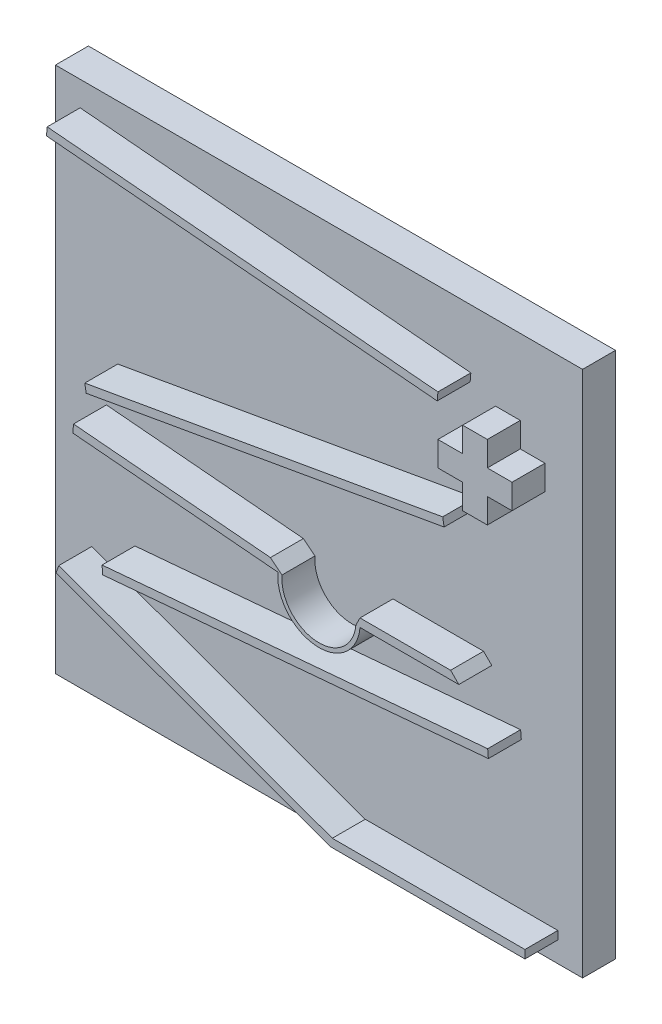
SolidWorks part; units mm, degrees
ref_plane "Front Plane" through (0, 0, 0) normal (0, 0, 1) x (1, 0, 0)
ref_plane "Top Plane" through (0, 0, 0) normal (0, 1, 0) x (1, 0, 0)
ref_plane "Right Plane" through (0, 0, 0) normal (1, 0, 0) x (0, 0, -1)
sketch "Sketch1" plane through (0, 0, 0) normal (0, 0, 1) x (1, 0, 0)
  line L0 (-348.7355, 289.6567) -> (-349.607, 279.6948)
  line L1 (-358.7355, 299.6567) -> (241.2645, 299.6567)
  line L2 (-358.7355, 299.6567) -> (-358.7355, -300.3433)
  line L3 (-358.7355, -300.3433) -> (241.2645, -300.3433)
  line L4 (241.2645, 299.6567) -> (241.2645, -300.3433)
  line L5 (-378.7355, 319.6567) -> (261.2645, 319.6567)
  line L6 (-378.7355, 319.6567) -> (-378.7355, -320.3433)
  line L7 (-378.7355, -320.3433) -> (261.2645, -320.3433)
  line L8 (261.2645, 319.6567) -> (261.2645, -320.3433)
  line L9 (-348.7355, 289.6567) -> (125.6342, 248.1548)
  line L10 (-349.607, 279.6948) -> (124.7627, 238.1928)
  line L11 (124.7627, 238.1928) -> (125.6342, 248.1548)
  line L12 (125.6342, 198.1548) -> (125.6342, 168.1548)
  line L13 (125.6342, 198.1548) -> (155.6342, 198.1548)
  line L14 (125.6342, 168.1548) -> (155.6342, 168.1548)
  line L15 (155.6342, 168.1548) -> (155.6342, 138.1548)
  line L16 (155.6342, 138.1548) -> (185.6342, 138.1548)
  line L17 (185.6342, 138.1548) -> (185.6342, 168.1548)
  line L18 (185.6342, 168.1548) -> (215.6342, 168.1548)
  line L19 (215.6342, 168.1548) -> (215.6342, 198.1548)
  line L20 (215.6342, 198.1548) -> (185.6342, 198.1548)
  line L21 (185.6342, 198.1548) -> (185.6342, 228.1548)
  line L22 (185.6342, 228.1548) -> (155.6342, 228.1548)
  line L23 (155.6342, 228.1548) -> (155.6342, 198.1548)
  line L24 (131.444, 119.6567) -> (-303.1276, 43.03)
  line L25 (-303.1276, 43.03) -> (-301.3911, 33.1819)
  line L26 (-301.3911, 33.1819) -> (133.1805, 109.8086)
  line L27 (131.444, 119.6567) -> (133.1805, 109.8086)
  line L28 (-316.7965, -6.8181) -> (-77.7098, -27.7354)
  line L29 (-316.7965, -6.8181) -> (-317.6681, -16.78)
  line L30 (-317.6681, -16.78) -> (-68.6194, -38.5689)
  line L31 (-77.7098, -27.7354) -> (-63.6384, -39.0047)
  line L32 (-316.7965, -6.8181) -> (-264.7629, -6.8181) construction
  line L33 (31.0363, -46.8487) -> (151.0363, -46.8487)
  line L34 (31.0363, -36.8487) -> (141.0363, -36.8487)
  line L35 (141.0363, -36.8487) -> (151.0363, -46.8487)
  line L36 (186.0363, -96.8487) -> (-282.1752, -137.8119)
  line L37 (26.0191, -46.8487) -> (31.0363, -36.8487)
  line L38 (-282.1752, -137.8119) -> (-281.3037, -147.7739)
  line L39 (-281.3037, -147.7739) -> (186.9078, -106.8107)
  line L40 (186.0363, -96.8487) -> (186.9078, -106.8107)
  line L41 (186.0363, -96.8487) -> (134.5722, -96.8487) construction
  line L42 (-334.5739, -164.5144) -> (-2.5993, -285.3433)
  line L43 (231.2645, -285.3433) -> (231.2645, -295.3433)
  line L44 (-4.3626, -295.3433) -> (-337.9941, -173.9113)
  line L45 (-337.9941, -173.9113) -> (-334.5739, -164.5144)
  line L46 (-334.5739, -164.5144) -> (-283.0811, -164.5144) construction
  line L47 (-2.5993, -285.3433) -> (231.2645, -285.3433)
  line L48 (-4.3626, -295.3433) -> (231.2645, -295.3433)
  arc A0 (-68.6194, -38.5689) -> (31.0363, -46.8487) centre (-18.8097, -42.9267) ccw
  arc A1 (-63.6384, -39.0047) -> (26.0191, -46.8487) centre (-18.8097, -42.9267) ccw
  point P0 (0, 0)
  point P6 (0, 0)
  point P50 (0, 0)
  point P57 (0, 0)
  point P58 (0, 0)
  point P59 (230.0478, -295.3433)
  dimension "D15" = 40
  dimension "D18" = 100
  dimension "D19" = 90
  dimension "D1" = 600
  dimension "D2" = 600
  dimension "D3" = 20
  dimension "D4" = 640
  dimension "D5" = 20
  dimension "D6" = 640
  dimension "D7" = 5
  dimension "D8" = 10
  dimension "D9" = 10
  dimension "D10" = 10
  dimension "D11" = 30
  dimension "D12" = 20
  dimension "D13" = 30
  dimension "D14" = 10
  dimension "D16" = 180
  dimension "D17" = 250
  dimension "D20" = 240
  dimension "D21" = 5
  dimension "D22" = 10
  dimension "D23" = 120
  dimension "D24" = 110
  dimension "D25" = 50
  dimension "D26" = 35
  dimension "D27" = 470
  dimension "D28" = 5
  dimension "D29" = 20
  dimension "D30" = 5
  dimension "D31" = 10
  dimension "D32" = 10
extrude "Boss-Extrude2" add sketch "Sketch1" along normal blind 40 separate body contours L22 L23 L13 L12 L14 L15 L16 L17 L18 L19 L20 L21 | L10 L11 L9 L0 | L26 L27 L24 L25 | L28 L31 A1 L37 L34 L35 L33 A0 L30 L29 | L36 L38 L39 L40 | L42 L47 L43 L48 L44 L45 region at (170.6342, 183.1548, 0)
extrude "Boss-Extrude3" add sketch "Sketch1<4>" against normal blind 40 separate body contours L4 L1 L2 L3 L48 L44 L45 L42 L47 L43 L23 L22 L21 L20 L19 L18 L17 L16 L15 L14 L12 L13 L11 L10 L0 L9 L24 L27 L26 L25 L36 L40 L39 L38 L31 A1 L37 L34 L35 L33 A0 L30 L29 L28 | L8 L5 L6 L7 L1 L4 L3 L2 region at (-60.5207, -0.9404, 0) region at (-58.7355, 310.6058, 0)
sketch "Sketch1<4>" plane through (0, 0, 0) normal (0, 0, 1) x (1, 0, 0) same geometry as "Sketch1"
